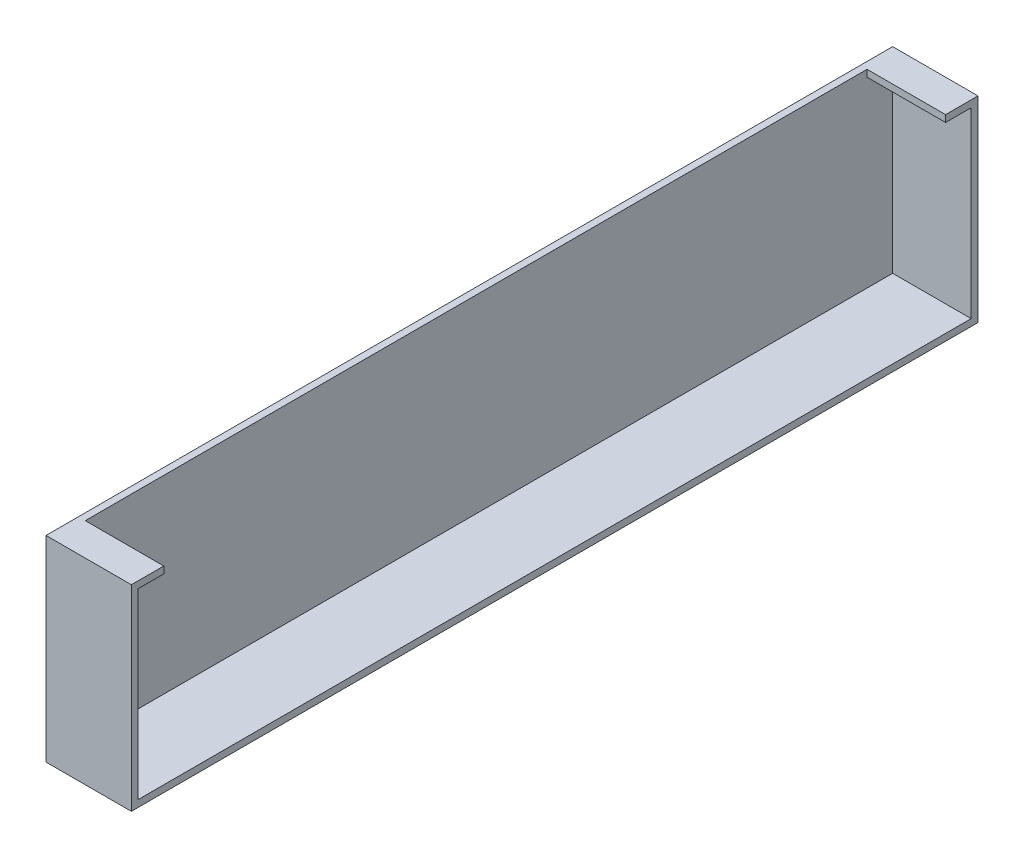
SolidWorks part; units mm, degrees
ref_plane "Alzado" through (0, 0, 0) normal (0, 0, 1) x (1, 0, 0)
ref_plane "Planta" through (0, 0, 0) normal (0, 1, 0) x (1, 0, 0)
ref_plane "Vista lateral" through (0, 0, 0) normal (1, 0, 0) x (0, 0, -1)
sketch "Croquis1" plane through (0, 0, 0) normal (0, 0, 1) x (1, 0, 0)
  line L0 (0, 0) -> (0, 115)
  line L1 (0, 0) -> (50, 0)
  line L2 (4, 4) -> (50, 4)
  line L3 (4, 4) -> (4, 115)
  line L4 (0, 115) -> (4, 115)
  line L5 (50, 4) -> (50, 0)
  dimension "D1" = 115
  dimension "D2" = 50
  dimension "D3" = 4
extrude "Saliente-Extruir1" add sketch "Croquis1" along normal blind 248 and the other way blind 248
sketch "Croquis2" plane through (0, 0, 248) normal (0, 0, 1) x (1, 0, 0)
  line L0 (0, 57.5) -> (25, 57.5) construction
  line L1 (0, 115) -> (0, 0) construction
  line L2 (25, 57.5) -> (25, 0) construction
  line L3 (0, 0) -> (50, 0) construction
  line L5 (0, 115) -> (50, 115)
  line L6 (0, 115) -> (0, 0)
  line L7 (0, 0) -> (50, 0)
  line L8 (50, 115) -> (50, 0)
  line L9 (0, 115) -> (50, 0) construction
  line L10 (0, 0) -> (50, 115) construction
extrude "Saliente-Extruir2" add sketch "Croquis2" against normal blind 4
sketch "Croquis3" plane through (50, 0, 0) normal (1, 0, 0) x (0, 0, -1)
  line L0 (248, 0) -> (-248, 0) construction
  line L1 (-248, 0) -> (-248, 115) construction
  line L2 (248, 0) -> (-248, 0)
  line L3 (-248, 0) -> (-248, 115)
  line L4 (-248, 0) -> (-300.4, 0)
  line L5 (-300.4, 0) -> (-300.4, 57.5)
  line L6 (-300.4, 57.5) -> (-248, 57.5)
  line L7 (-316.3335, 50) -> (-127.1391, 50) construction
  line L8 (-332.8582, 21.988) -> (-171.3057, 21.988) construction
  dimension "D1" = 52.4
mirror "Simetría1" about plane through (0, 0, 0) normal (0, 0, 1) of "Saliente-Extruir2"
sketch "Croquis5" plane through (0, 115, 0) normal (0, 1, 0) x (1, 0, 0)
  line L0 (50, -244) -> (4, -244) construction
  line L1 (50, -244) -> (4, -244)
  line L3 (50, -244) -> (4, -244)
  line L4 (50, -244) -> (50, -229)
  line L5 (50, -229) -> (4, -229)
  line L6 (4, -244) -> (4, -229)
  line L7 (4, 244) -> (4, -244) construction
  line M12 (50, -244) -> (4, -244)
  dimension "D1" = 15
extrude "Saliente-Extruir5" add sketch "Croquis5" against normal blind 4 contours L4 L5 M12 region at (27, 115, 236.5)
mirror "Simetría2" about plane through (0, 0, 0) normal (0, 0, 1) of "Saliente-Extruir5"
sketch "Croquis6" plane through (0, 0, 0) normal (-1, 0, 0) x (0, 0, 1)
  circle A1 centre (-275, 31.3) radius 6 construction
  circle A2 centre (-275, 31.3) radius 15
  circle A3 centre (-275, 31.3) radius 6 construction
  dimension "D1" = 30
sketch "Croquis7" plane through (50, 0, 0) normal (1, 0, 0) x (0, 0, -1)
  circle A1 centre (-275, 31.3) radius 6 construction
  circle A2 centre (-275, 31.3) radius 15
  circle A3 centre (-275, 31.3) radius 6 construction
  dimension "D1" = 30
